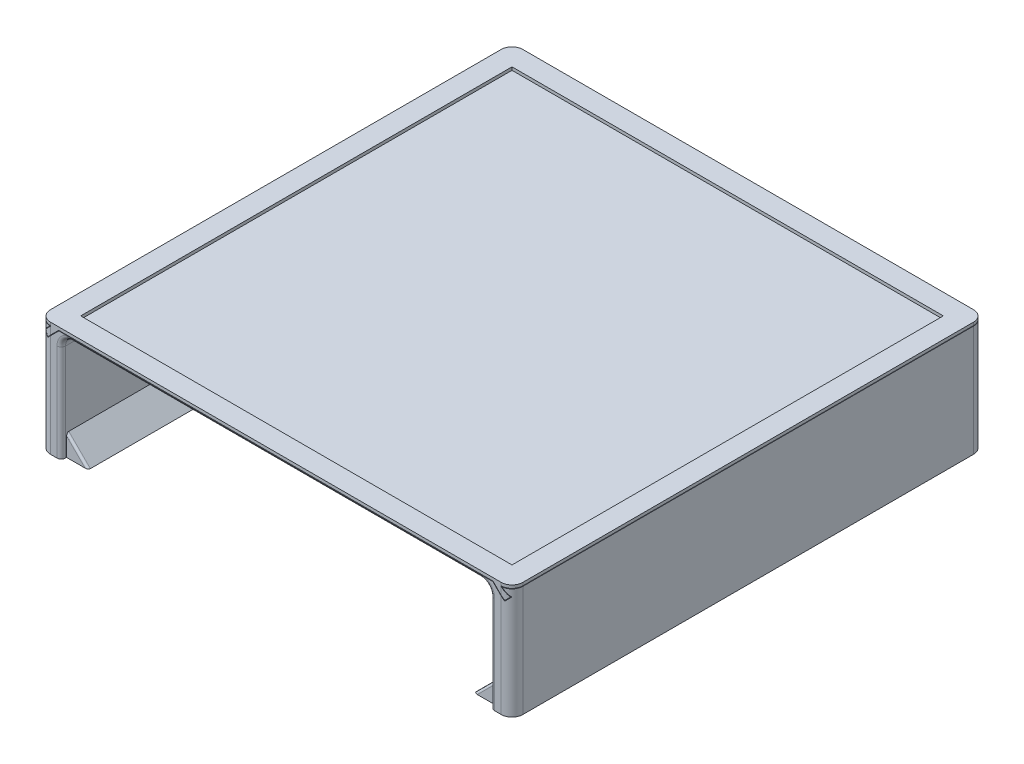
SolidWorks part; units mm, degrees
ref_plane "Front Plane" through (0, 0, 0) normal (0, 0, 1) x (1, 0, 0)
ref_plane "Top Plane" through (0, 0, 0) normal (0, 1, 0) x (1, 0, 0)
ref_plane "Right Plane" through (0, 0, 0) normal (1, 0, 0) x (0, 0, -1)
sketch "Sketch1" plane through (0, 0, 0) normal (0, 0, 1) x (1, 0, 0)
  line L0 (-99.5, -1.5) -> (99.5, -1.5)
  line L1 (-109.5, -51.5) -> (-99.5, -51.5)
  line L2 (-109.5, -51.5) -> (-109.5, 0)
  line L4 (-99.5, -51.5) -> (-99.5, -1.5)
  line L5 (0, -1.5) -> (0, 0) construction
  line L10 (-109.5, 0.2) -> (-104.2343, 0.2)
  line L14 (-100.6988, 0.2) -> (100.6988, 0.2)
  line L15 (0, 0.2) -> (0, 1.6) construction
  line L16 (109.5, 1.6) -> (-109.5, 1.6)
  line L17 (-109.5, 1.6) -> (-109.5, 0.2)
  line L21 (-109.5, 0) -> (-104.7172, 0)
  line L22 (-100.6159, 0) -> (100.6159, 0)
  line L23 (109.5, 1.2) -> (-109.5, 1.2) construction
  line L24 (109.5, 0) -> (104.7172, 0)
  line L28 (109.5, 1.6) -> (109.5, 0.2)
  line L29 (109.5, 0.2) -> (104.2343, 0.2)
  line L33 (99.5, -51.5) -> (99.5, -1.5)
  line L34 (109.5, -51.5) -> (109.5, 0)
  line L35 (109.5, -51.5) -> (99.5, -51.5)
  line L36 (-100.5, 0.2) -> (-100.5, 1.2) construction
  line L37 (-100.6988, 0.2) -> (-105.9494, -5.0506)
  line L38 (-105.9494, -5.0506) -> (-107.7172, -3.2828)
  line L39 (-107.7172, -3.2828) -> (-104.2343, 0.2)
  line L40 (-104.7172, 0) -> (-108, -3.2828)
  line L41 (-108, -3.2828) -> (-105.9494, -5.3335)
  line L42 (-105.9494, -5.3335) -> (-100.6159, 0)
  line L43 (-106.9747, -4.3081) -> (-106.8333, -4.1667) construction
  line L44 (100.6988, 0.2) -> (105.9494, -5.0506)
  line L45 (105.9494, -5.3335) -> (100.6159, 0)
  line L46 (108, -3.2828) -> (105.9494, -5.3335)
  line L47 (105.9494, -5.0506) -> (107.7172, -3.2828)
  line L48 (107.7172, -3.2828) -> (104.2343, 0.2)
  line L49 (104.7172, 0) -> (108, -3.2828)
  point P21 (0, 1.2)
  dimension "D1" = 109.5
  dimension "D5" = 0.2
  dimension "D9" = 0.4
  dimension "MetalSheetGap" = 1
  dimension "D11" = 10
  dimension "MainBoardSize" = 50
  dimension "D13" = 9
  dimension "D3" = 45
  dimension "D4" = 1.5
  dimension "D2" = 2.5
  dimension "D7" = 0.2
  dimension "D8" = 0.2
  dimension "D10" = 3
  dimension "D6" = 1.5
extrude "Boss-Extrude1" add sketch "Sketch1" along normal mid plane 219 contours L4 L0 L33 L35 L34 L24 L49 L46 L45 L22 L42 L41 L40 L21 L2 L1
extrude "Boss-Extrude2" add sketch "Sketch1<4>" along normal mid plane 219 separate body contours L16 L17 L10 L39 L38 L37 L14 L44 L47 L48 L29 L28
sketch "Sketch1<4>" plane through (0, 0, 0) normal (0, 0, 1) x (1, 0, 0) same geometry as "Sketch1"
sketch "Sketch2" plane through (0, 0.2, 0) normal (0, -1, 0) x (1, 0, 0)
  line L1 (-100, -100) -> (100, -100)
  line L2 (-100, -100) -> (-100, 100)
  line L3 (-100, 100) -> (100, 100)
  line L4 (100, -100) -> (100, 100)
  line L5 (-100, -100) -> (100, 100) construction
  line L6 (-100, 100) -> (100, -100) construction
  point P0 (0, 0)
  dimension "D1" = 200
  dimension "D2" = 200
extrude "Cut-Extrude1" cut sketch "Sketch2" against normal through all contours L3 L4 L1 L2
fillet "Fillet1" radius 5 2 edges at (99.5, -1.5, 0) (-99.5, -1.5, 0)
sketch "Sketch3" plane through (0, 0, 0) normal (0, 0, 1) x (1, 0, 0)
  line L1 (-99.5, -1.5) -> (99.5, -1.5)
  line L2 (-99.5, -1.5) -> (-99.5, -51.5)
  line L3 (-99.5, -51.5) -> (99.5, -51.5)
  line L4 (99.5, -1.5) -> (99.5, -51.5)
extrude "Boss-Extrude3" add sketch "Sketch3" along normal mid plane 10
fillet "Fillet2" radius 5 4 edges at (-109.5, -25.75, 109.5) (-109.5, -25.75, -109.5) (109.5, -25.75, -109.5) (109.5, -25.75, 109.5)
sketch "Sketch9" plane through (0, -51.5, 0) normal (0, -1, 0) x (1, 0, 0)
  line L0 (104.5, -109.5) -> (-104.5, -109.5)
  line L1 (-109.5, -104.5) -> (-109.5, 104.5)
  line L2 (-104.5, 109.5) -> (104.5, 109.5)
  line L3 (109.5, 104.5) -> (109.5, -104.5)
  line L5 (-189.5, 189.5) -> (189.5, 189.5)
  line L6 (-189.5, 189.5) -> (-189.5, -189.5)
  line L7 (-189.5, -189.5) -> (189.5, -189.5)
  line L8 (189.5, 189.5) -> (189.5, -189.5)
  line L9 (-189.5, 189.5) -> (189.5, -189.5) construction
  line L10 (-189.5, -189.5) -> (189.5, 189.5) construction
  arc A0 (-104.5, 109.5) -> (-109.5, 104.5) centre (-104.5, 104.5) ccw
  arc A1 (-104.5, 109.5) -> (-109.5, 104.5) centre (-104.5, 104.5) ccw
  arc A2 (109.5, 104.5) -> (104.5, 109.5) centre (104.5, 104.5) ccw
  arc A3 (109.5, 104.5) -> (104.5, 109.5) centre (104.5, 104.5) ccw
  arc A4 (104.5, -109.5) -> (109.5, -104.5) centre (104.5, -104.5) ccw
  arc A5 (104.5, -109.5) -> (109.5, -104.5) centre (104.5, -104.5) ccw
  arc A6 (-109.5, -104.5) -> (-104.5, -109.5) centre (-104.5, -104.5) ccw
  arc A7 (-109.5, -104.5) -> (-104.5, -109.5) centre (-104.5, -104.5) ccw
  point P7 (0, 0)
  line M9 (-99.5, 109.5) -> (-104.5, 109.5)
  arc M10 (-104.5, 109.5) -> (-109.5, 104.5) centre (-104.5, 104.5) ccw
  line M11 (-109.5, 104.5) -> (-109.5, -104.5)
  arc M12 (-109.5, -104.5) -> (-104.5, -109.5) centre (-104.5, -104.5) ccw
  line M13 (-104.5, -109.5) -> (-99.5, -109.5)
  line M17 (99.5, -109.5) -> (104.5, -109.5)
  arc M18 (104.5, -109.5) -> (109.5, -104.5) centre (104.5, -104.5) ccw
  line M19 (109.5, -104.5) -> (109.5, 104.5)
  arc M20 (109.5, 104.5) -> (104.5, 109.5) centre (104.5, 104.5) ccw
  line M21 (104.5, 109.5) -> (99.5, 109.5)
  dimension "D1" = 80
extrude "Cut-Extrude3" cut sketch "Sketch9" against normal through all contours L8 L5 L6 L7 L2 L0 M9 M21 M20 M19 M18 M17 M13 M12 M11 M10 region at (0, -51.5, 184.1401)
fillet "Fillet4" radius 2 10 edges at (-99.5, -29, 109.5) (-98.0355, -2.9645, 109.5) (99.5, -29, 109.5) (98.0355, -2.9645, 109.5) (-99.5, -29, -109.5) (-98.0355, -2.9645, -109.5) (99.5, -29, -109.5) (98.0355, -2.9645, -109.5) (0, -1.5, 109.5) (0, -1.5, -109.5)
fillet "Fillet5" radius 1 10 edges at (-99.5, -29, -5) (-98.0355, -2.9645, -5) (0, -1.5, -5) (98.0355, -2.9645, -5) (-99.5, -29, 5) (-98.0355, -2.9645, 5) (0, -1.5, 5) (98.0355, -2.9645, 5) (99.5, -29, -5) (99.5, -29, 5)
sketch "Sketch6" plane through (0, 0, 0) normal (0, 0, 1) x (1, 0, 0)
  line L0 (-99.5, -51.5) -> (-89.5, -51.5)
  line L1 (-98.5, -51.5) -> (98.5, -51.5) construction
  line L2 (-89.5, -51.5) -> (-99.5, -41.5)
  line L3 (-99.5, -41.5) -> (-99.5, -51.5)
  dimension "D1" = 45
  dimension "D2" = 10
extrude "Boss-Extrude6" add sketch "Sketch6" against normal mid plane 214
fillet "Fillet6" radius 1 2 edges at (-94.5, -46.5, 107) (-94.5, -46.5, -107)
mirror "Mirror1" about plane through (0, 0, 0) normal (1, 0, 0) of "Fillet6", "Boss-Extrude6"
sketch "Sketch10" plane through (0, 0, 0) normal (0, 0, 1) x (1, 0, 0)
  line L0 (-10, -27) -> (-10, -37)
  line L1 (10, -17) -> (-10, -17)
  line L2 (10, -17) -> (10, -27)
  line L4 (-10, -17) -> (-10, -27)
  line L5 (-10, -37) -> (10, -37)
  line L6 (10, -37) -> (10, -27)
  arc A0 (10, -27) -> (-10, -27) centre (0, -27) cw
  arc A1 (-10, -27) -> (10, -27) centre (0, -27) cw
extrude "Cut-Extrude4" cut sketch "Sketch10" against normal mid plane 4.1 contours A1 A0 | L5 A0 L0 | L6 A0 L5 region at (-7.7663, -34.7663, 0) region at (0, -27, 0) region at (7.7663, -34.7663, 0)
pattern_linear "LPattern1" count 2 spacing 22 along (1, 0, 0) count 2 spacing 22 along (-1, 0, 0) of "Cut-Extrude4" pattern seed only yes
equation "\"CheckerPatternThickness\"= 0.2mm * 2'How thick the squares the pecies sit on should be"
equation "\"D9@Sketch1\"=\"CheckerPatternThickness\""
equation "\"D2@Sketch2\"=\"D1@Sketch2\""
equation "\"D7@Sketch1\"=\"D5@Sketch1\""
equation "\"D8@Sketch1\"=\"D5@Sketch1\""
